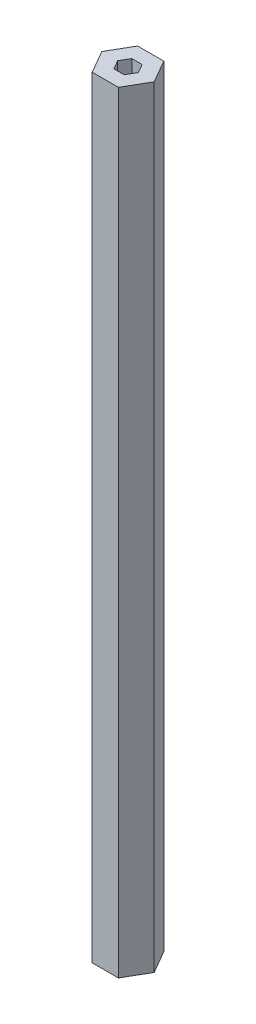
SolidWorks part; units mm, degrees
ref_plane "Front Plane" through (0, 0, 0) normal (0, 0, 1) x (1, 0, 0)
ref_plane "Top Plane" through (0, 0, 0) normal (0, 1, 0) x (1, 0, 0)
ref_plane "Right Plane" through (0, 0, 0) normal (1, 0, 0) x (0, 0, -1)
sketch "Sketch1" plane through (0, 0, 0) normal (0, 1, 0) x (1, 0, 0)
  line L9 (7.3323, 0) -> (3.6662, 6.35)
  line L10 (3.6662, 6.35) -> (-3.6662, 6.35)
  line L11 (-3.6662, 6.35) -> (-7.3323, 0)
  line L12 (-7.3323, 0) -> (-3.6662, -6.35)
  line L13 (-3.6662, -6.35) -> (3.6662, -6.35)
  line L14 (3.6662, -6.35) -> (7.3323, 0)
  line L15 (1.4434, 2.5) -> (-1.4434, 2.5)
  line L16 (-1.4434, 2.5) -> (-2.8868, 0)
  line L17 (-2.8868, 0) -> (-1.4434, -2.5)
  line L18 (-1.4434, -2.5) -> (1.4434, -2.5)
  line L19 (1.4434, -2.5) -> (2.8868, 0)
  line L20 (2.8868, 0) -> (1.4434, 2.5)
  circle A0 centre (0, 0) radius 6.35 construction
  circle A1 centre (0, 0) radius 2.5 construction
  dimension "D1" = 12.7
  dimension "D2" = 5
extrude "Boss-Extrude1" add sketch "Sketch1" along normal blind 215.9
